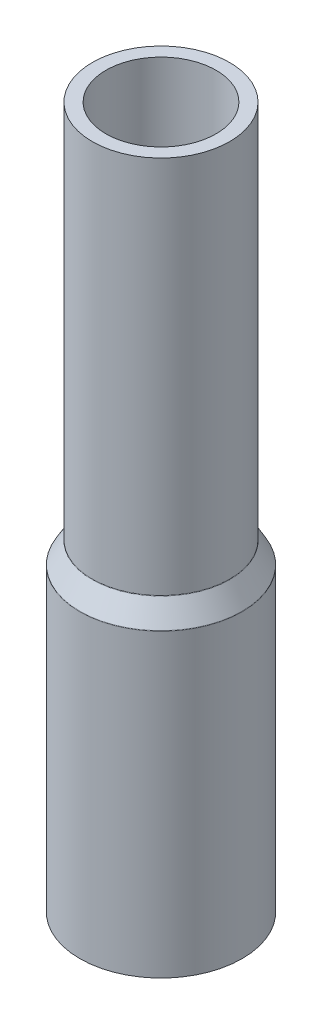
SolidWorks part; units mm, degrees
material "PE High Density"
ref_plane "Front Plane" through (0, 0, 0) normal (0, 0, 1) x (1, 0, 0)
ref_plane "Top Plane" through (0, 0, 0) normal (0, 1, 0) x (1, 0, 0)
ref_plane "Right Plane" through (0, 0, 0) normal (1, 0, 0) x (0, 0, -1)
sketch "Sketch1" plane through (0, 0, 0) normal (0, 1, 0) x (1, 0, 0)
  circle A0 centre (0, 0) radius 0.81
  circle A1 centre (0, 0) radius 0.685
  dimension "D1" = 1.62
  dimension "D2" = 1.37
extrude "Boss-Extrude1" add sketch "Sketch1" along normal blind 3
sketch "Sketch2" plane through (0, 3, 0) normal (0, 1, 0) x (1, 0, 0)
  circle A0 centre (0, 0) radius 0.55
  circle A1 centre (0, 0) radius 0.685
  circle A2 centre (0, 0) radius 0.685 construction
  dimension "D1" = 1.1
extrude "Boss-Extrude2" add sketch "Sketch2" along normal blind 4 separate body
sketch "Sketch3" plane through (0, 0, 0) normal (0, 0, 1) x (1, 0, 0)
  line L0 (0, 0) -> (0, 8.1367) construction
  line L1 (-0.81, 3) -> (-0.685, 3.2165)
  line L2 (-0.685, 7) -> (-0.685, 3) construction
  line L3 (-0.685, 3.2165) -> (-0.685, 3)
  line L4 (0.81, 3) -> (-0.81, 3) construction
  line L5 (-0.685, 3) -> (-0.81, 3)
  dimension "D1" = 60
revolve "Revolve1" add sketch "Sketch3" angle 360 about L0
fillet "Fillet1" radius 0.01 1 edges at (0, 3, 0.81)
fillet "Fillet2" radius 0.01 1 edges at (0, 3.2165, -0.685)
ref_plane "Plane1" through (0, 0, 0.55) normal (0, 0, 1) x (1, 0, 0)
sketch "Sketch4" plane through (0, 0, 0.55) normal (0, 0, 1) x (1, 0, 0)
  line L0 (0, 0) -> (0, 7) construction
  line L1 (-0.685, 0) -> (0.685, 0) construction
  line L2 (0.55, 7) -> (-0.55, 7) construction
